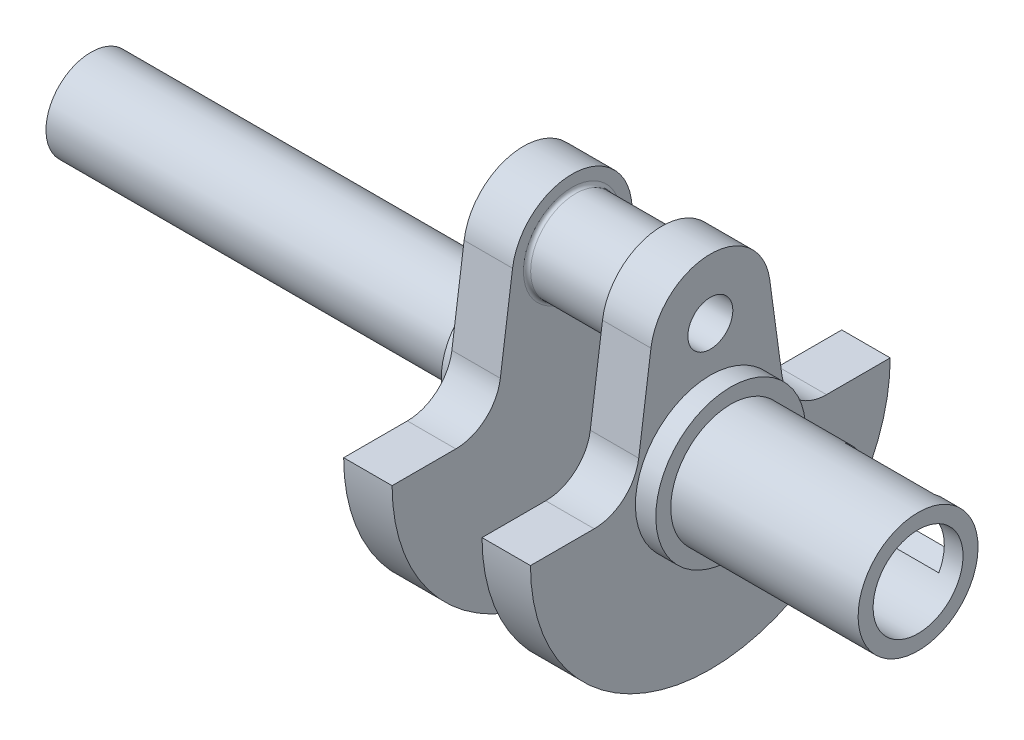
SolidWorks part; units mm, degrees
ref_plane "Front Plane" through (0, 0, 0) normal (0, 0, 1) x (1, 0, 0)
ref_plane "Top Plane" through (0, 0, 0) normal (0, 1, 0) x (1, 0, 0)
ref_plane "Right Plane" through (0, 0, 0) normal (1, 0, 0) x (0, 0, -1)
sketch "Sketch1" plane through (0, 0, 0) normal (0, 0, 1) x (1, 0, 0)
  line L0 (0, 0) -> (-22.7874, 0) construction
  line L1 (-43.6562, 0) -> (-43.6562, 4.7625)
  line L2 (-43.6562, 4.7625) -> (0, 4.7625)
  line L3 (0, 4.7625) -> (0, 6.5484)
  line L4 (0, 6.5484) -> (2.159, 6.5484)
  line L5 (2.159, 6.5484) -> (2.159, 19.05)
  line L6 (2.159, 19.05) -> (7.2898, 19.05)
  line L7 (7.2898, 19.05) -> (7.2898, 0)
  line L8 (16.8148, 4.7625) -> (16.8148, 19.05)
  line L9 (16.8148, 19.05) -> (21.9456, 19.05)
  line L10 (21.9456, 19.05) -> (21.9456, 7.9375)
  line L11 (21.9456, 7.9375) -> (24.1046, 7.9375)
  line L12 (24.1046, 7.9375) -> (24.1046, 6.35)
  line L13 (24.1046, 6.35) -> (43.9484, 6.35)
  line L14 (43.9484, 6.35) -> (43.9484, 4.7625)
  line L18 (7.2898, 0) -> (-43.6562, 0)
  line L19 (43.9484, 4.7625) -> (16.8148, 4.7625)
  dimension "D1" = 9.525
  dimension "D2" = 13.0969
  dimension "D3" = 38.1
  dimension "D4" = 43.6562
  dimension "D5" = 2.159
  dimension "D6" = 5.1308
  dimension "D7" = 9.525
  dimension "D8" = 15.875
  dimension "D9" = 12.7
  dimension "D10" = 9.525
  dimension "D11" = 19.8438
  dimension "D12" = 2.159
revolve "Revolve1" add sketch "Sketch1" angle 360 about L0
ref_axis "Axis1" through (-43.6562, 0, 0) along (1, 0, 0)
sketch "Sketch2" plane through (0, 0, 0) normal (0, 0, 1) x (1, 0, 0)
  line L0 (-15.5535, 12.7) -> (42.3581, 12.7) construction
  line L1 (-43.6562, 0) -> (46.6651, 0) construction
  line L2 (7.2898, 17.4561) -> (16.8148, 17.4561)
  line L3 (7.2898, -19.05) -> (7.2898, 19.05) construction
  line L4 (16.8148, 19.05) -> (16.8148, -19.05) construction
  line L5 (16.8148, 17.4561) -> (16.8148, 12.7)
  line L6 (16.8148, 12.7) -> (7.2898, 12.7)
  line L7 (7.2898, 12.7) -> (7.2898, 17.4561)
  dimension "D1" = 12.7
  dimension "D2" = 9.5123
revolve "Revolve2" add sketch "Sketch2" angle 360 about L0
sketch "Sketch3" plane through (7.2898, 0, 0) normal (1, 0, 0) x (0, 0, -1)
  line L0 (0, 0) -> (0, 19.05) construction
  line L1 (0, 0) -> (17.9011, 6.5155) construction
  circle A0 centre (0, 0) radius 19.05 construction
  point P6 (18.8895, 2.4673)
  dimension "D1" = 70
ref_plane "Plane1" through (7.2898, 6.5155, -17.9011) normal (0, 0.342, -0.9397) x (-1, 0, 0)
sketch "Sketch4" plane through (7.2898, 6.5155, -17.9011) normal (0, 0.342, -0.9397) x (-1, 0, 0)
  line L0 (50.9461, 0) -> (-39.3753, 0) construction
  line L1 (-34.6742, 3.5719) -> (-25.1492, 3.5719)
  line L2 (-34.6742, 3.5719) -> (-34.6742, -3.5719)
  line L3 (-34.6742, -3.5719) -> (-25.1492, -3.5719)
  line L4 (-25.1492, 3.5719) -> (-25.1492, -3.5719)
  line L5 (-34.6742, 3.5719) -> (-25.1492, -3.5719) construction
  line L6 (-34.6742, -3.5719) -> (-25.1492, 3.5719) construction
  line L7 (-16.8148, 6.35) -> (-16.8148, -6.35) construction
  point P0 (-29.9117, 0)
  dimension "D1" = 7.1437
  dimension "D2" = 9.525
  dimension "D3" = 8.3344
extrude "Cut-Extrude1" cut sketch "Sketch4" against normal up to next and the other way through all
fillet "Fillet1" radius 0.381 2 edges at (16.8148, 12.7, 4.7561) (7.2898, 12.7, 4.7561)
ref_axis "Axis2" through (16.4338, 12.7, 0) along (-1, 0, 0)
sketch "Sketch5" plane through (21.9456, 0, 0) normal (1, 0, 0) x (0, 0, -1)
  line L0 (0, 19.05) -> (0, -19.05) construction
  line L1 (12.3031, 0) -> (19.05, 0)
  line L2 (-7.5847, 4.1164) -> (-6.2913, 13.5615)
  line L3 (-12.3031, 0) -> (-19.05, 0)
  line L4 (7.5847, 4.1164) -> (6.2913, 13.5615)
  circle A0 centre (0, 0) radius 19.05 construction
  arc A1 (-12.3031, 0) -> (-7.5847, 4.1164) centre (-12.3031, 4.7625) ccw
  arc A2 (6.2913, 13.5615) -> (-6.2913, 13.5615) centre (0, 12.7) ccw
  arc A3 (-19.05, 0) -> (19.05, 0) centre (0, 0) ccw construction
  arc A4 (12.3031, 0) -> (7.5847, 4.1164) centre (12.3031, 4.7625) cw
  arc A5 (-19.05, 0) -> (19.05, 0) centre (0, 0) cw
  circle M1 centre (0, 0) radius 19.05
  dimension "D1" = 9.525
  dimension "D4" = 12.7
  dimension "D2" = 12.3031
  dimension "D3" = 4.7625
extrude "Cut-Extrude2" cut sketch "Sketch5" against normal through all both and the other way through all contours A2 L3 A1 L2 M1 | A4 L1 A2 L4 M1 region at (21.9456, 7.9417, -11.752) region at (21.9456, 7.9417, 11.752)
sketch "Sketch6" plane through (2.159, 0, 0) normal (-1, 0, 0) x (0, 0, 1)
  arc A0 (6.2913, 13.5615) -> (-6.2913, 13.5615) centre (0, 12.7) ccw construction
  point P0 (0, 12.7)
hole_wizard "3/16 (0.1875) Diameter Hole1" positions "Sketch6" profile "Sketch7" hole size "3/16" standard "ANSI Inch" end condition through all
sketch "Sketch7" plane through (2.159, 12.7, 0) normal (0, 1, 0) x (0, 0, 1)
  line L0 (0, 0) -> (0, 41.7894)
  line L1 (0, 41.7894) -> (2.3812, 41.7894)
  line L2 (2.3812, 41.7894) -> (2.3812, 0)
  line L5 (2.3812, 0) -> (0, 0)
  line L11 (0, -6.35) -> (0, 107.95) construction
  dimension "Thru Hole Dia." = 4.7625
  dimension "Thru Hole Depth" = 41.7894
